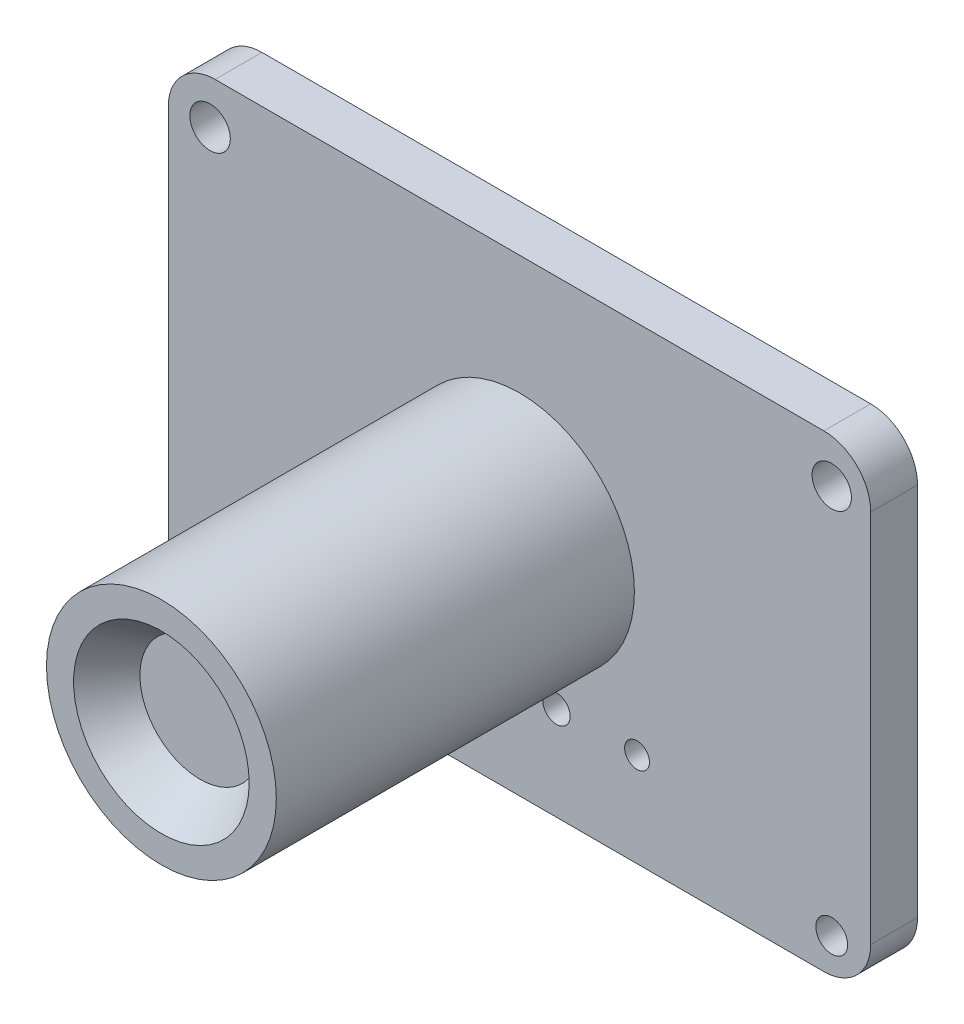
SolidWorks part; units mm, degrees
ref_plane "Front Plane" through (0, 0, 0) normal (0, 0, 1) x (1, 0, 0)
ref_plane "Top Plane" through (0, 0, 0) normal (0, 1, 0) x (1, 0, 0)
ref_plane "Right Plane" through (0, 0, 0) normal (1, 0, 0) x (0, 0, -1)
sketch "Sketch1" plane through (0, 0, 0) normal (0, 0, 1) x (1, 0, 0)
  line L1 (-6.5, -5) -> (6.5, -5)
  line L2 (-7.5, -4) -> (-7.5, 4)
  line L3 (-6.5, 5) -> (6.5, 5)
  line L4 (7.5, -4) -> (7.5, 4)
  line L5 (-7.5, -5) -> (7.5, 5) construction
  line L6 (-7.5, 5) -> (7.5, -5) construction
  arc A0 (6.5, 5) -> (7.5, 4) centre (6.5, 4) cw
  arc A1 (6.5, -5) -> (7.5, -4) centre (6.5, -4) ccw
  arc A2 (-6.5, -5) -> (-7.5, -4) centre (-6.5, -4) cw
  arc A3 (-7.5, 4) -> (-6.5, 5) centre (-6.5, 4) cw
  point P0 (0, 0)
  dimension "D3" = 1
  dimension "D1" = 10
  dimension "D2" = 15
extrude "Boss-Extrude1" add sketch "Sketch1" along normal blind 1
sketch "Sketch2" plane through (0, 0, 1) normal (0, 0, 1) x (1, 0, 0)
  circle A0 centre (-6.607, 4.0617) radius 0.4321
  circle A1 centre (6.6677, 4.0617) radius 0.4199
  circle A2 centre (6.6677, -4.2527) radius 0.3397
  circle A3 centre (-6.607, -4.2527) radius 0.4114
  circle A4 centre (-2.74, -3.038) radius 0.3058
  circle A5 centre (-0.9111, -2.9907) radius 0.294
  circle A6 centre (0.7896, -2.9907) radius 0.2924
  circle A7 centre (2.5105, -2.9907) radius 0.2656
  circle A8 centre (0, 0) radius 2.4539
  point P19 (0, 0)
extrude "Cut-Extrude1" cut sketch "Sketch2" against normal blind 1 contours A3 | A4 | A5 | A6 | A7 | A2 | A1 | A0 region at (6.6677, 4.0617, 1) region at (6.6677, -4.2527, 1) region at (-6.607, -4.2527, 1) region at (-2.74, -3.038, 1) region at (-0.9111, -2.9907, 1) region at (0.7896, -2.9907, 1) region at (2.5105, -2.9907, 1)
extrude "Boss-Extrude2" add sketch "Sketch2<5>" along normal blind 4 contours A8
sketch "Sketch2<5>" plane through (0, 0, 1) normal (0, 0, 1) x (1, 0, 0) same geometry as "Sketch2"
sketch "Sketch6" plane through (0, 0, 0) normal (1, 0, 0) x (0, 0, -1)
  line L0 (-5, 2.4539) -> (-8.647, 2.4539)
  line L1 (-8.647, 2.4539) -> (-8.647, 1.8748)
  line L2 (-8.647, 1.8748) -> (-7.8235, 1.2809)
  line L3 (-7.8235, 1.2809) -> (-7.8235, 0)
  line L4 (-7.8235, 0) -> (-0.9703, 0) construction
  line L6 (-5, 2.4539) -> (-5, 0)
  line L7 (-5, 2.4539) -> (-5, -2.4539) construction
  line L8 (-5, 0) -> (-7.8235, 0)
revolve "Revolve1" add sketch "Sketch6" angle 360 about L4
